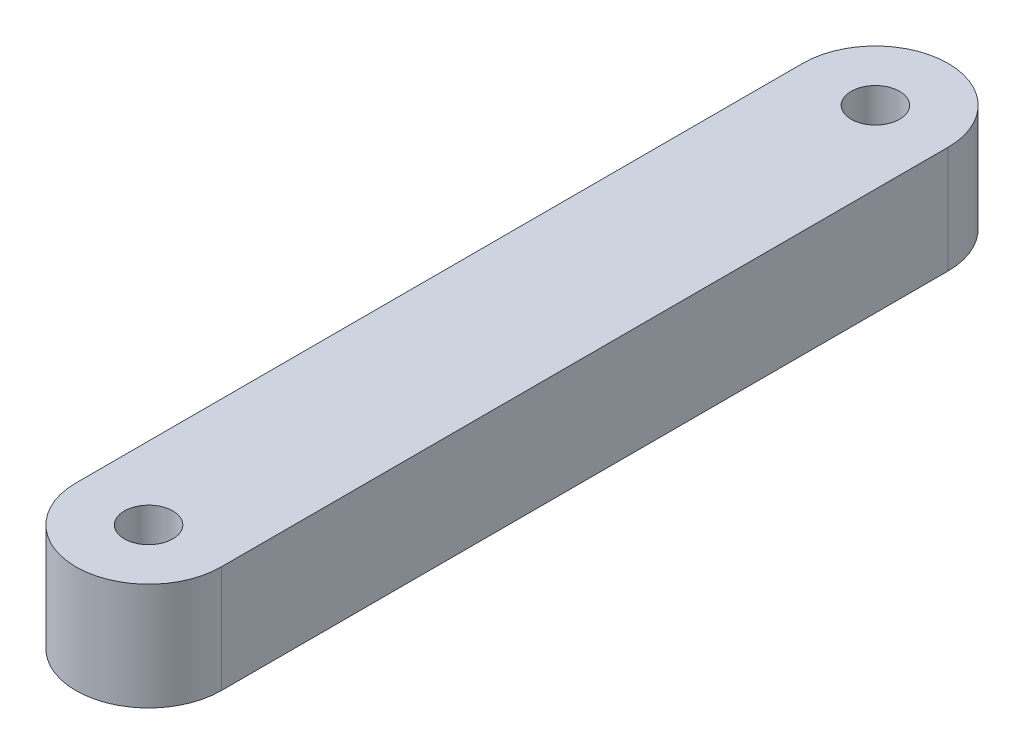
SolidWorks part; units mm, degrees
material "PLA Infill"
ref_plane "Front Plane" through (0, 0, 0) normal (0, 0, 1) x (1, 0, 0)
ref_plane "Top Plane" through (0, 0, 0) normal (0, 1, 0) x (1, 0, 0)
ref_plane "Right Plane" through (0, 0, 0) normal (1, 0, 0) x (0, 0, -1)
sketch "Sketch1" plane through (0, 0, 0) normal (0, 1, 0) x (1, 0, 0)
  line L0 (0, -60) -> (0, 60) construction
  line L1 (-12, -60) -> (-12, 60)
  line L2 (12, -60) -> (12, 60)
  arc A0 (-12, -60) -> (12, -60) centre (0, -60) ccw
  arc A1 (12, 60) -> (-12, 60) centre (0, 60) ccw
  circle A2 centre (0, 60) radius 4
  circle A3 centre (0, -60) radius 4
  point P2 (0, 0)
  dimension "D1" = 12
  dimension "D3" = 8
  dimension "D2" = 120
extrude "Boss-Extrude1" add sketch "Sketch1" along normal blind 17.7
